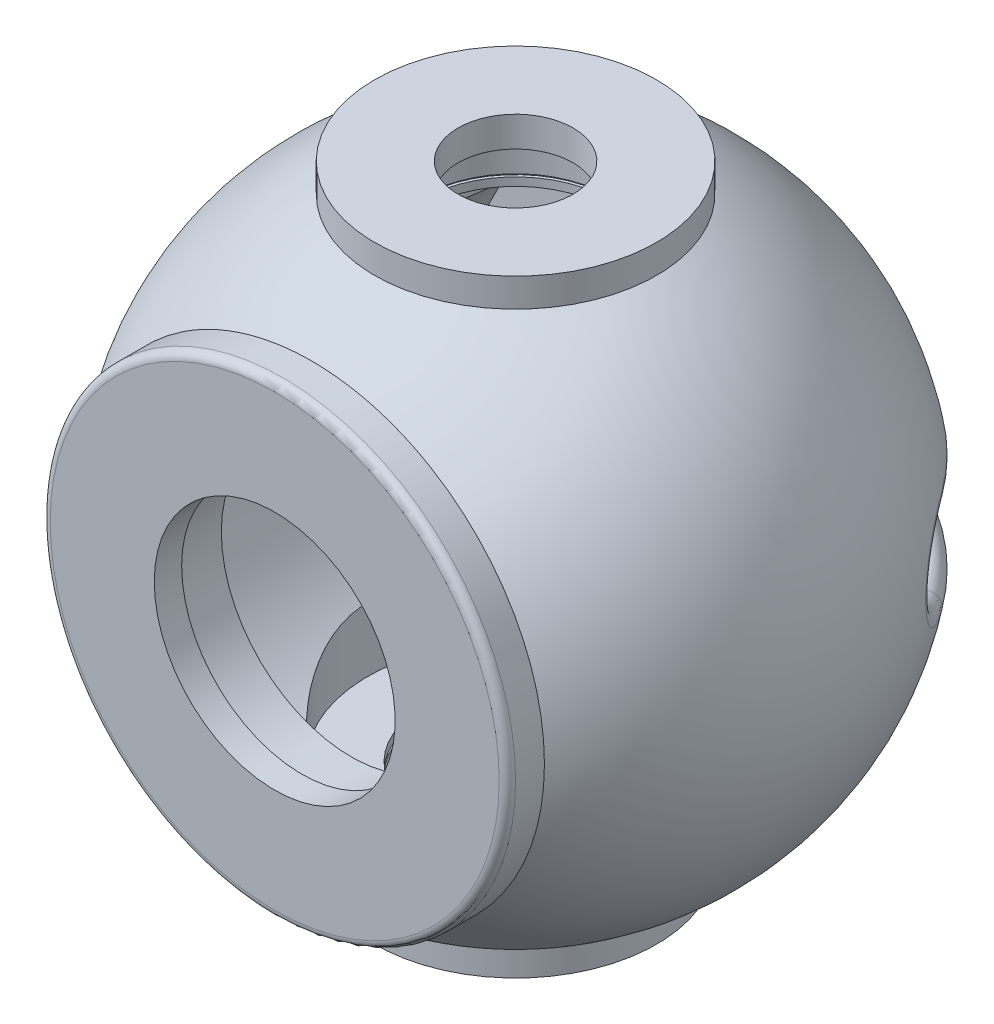
SolidWorks part; units mm, degrees
ref_plane "前视基准面" through (0, 0, 0) normal (0, 0, 1) x (1, 0, 0)
ref_plane "上视基准面" through (0, 0, 0) normal (0, 1, 0) x (1, 0, 0)
ref_plane "右视基准面" through (0, 0, 0) normal (1, 0, 0) x (0, 0, -1)
sketch "Sketch1" plane through (0, 0, 0) normal (0, 0, 1) x (1, 0, 0)
  line L0 (0, 113) -> (0, -113)
  arc A0 (0, -113) -> (0, 113) centre (0, 0) ccw
  dimension "D1" = 113
revolve "Revolve1" add sketch "Sketch1" angle 360 about L0
ref_plane "Plane1" through (0, 0, 120) normal (0, 0, 1) x (1, 0, 0)
sketch "Sketch5" plane through (0, 0, 0) normal (1, 0, 0) x (0, 0, -1)
  line L0 (0, 0) -> (0, 113) construction
  line L1 (31, 100) -> (21, 100)
  line L2 (31, 100) -> (31, 98)
  line L3 (31, 98) -> (34, 98)
  line L4 (34, 98) -> (34, 83)
  line L5 (34, 83) -> (35, 83)
  line L6 (35, 83) -> (35, 82)
  line L7 (35, 82) -> (34, 82)
  line L8 (34, 82) -> (34, 79)
  line L9 (21, 100) -> (21, 111.0315)
  line L10 (34, 79) -> (54, 79)
  line L11 (54, 79) -> (54, 0)
  line L12 (54, 0) -> (0, 0)
  line L13 (0, 0) -> (0, 113)
  line L14 (0, 0) -> (-48.9472, 0) construction
  circle A0 centre (0, 0) radius 113 construction
  arc A1 (21, 111.0315) -> (0, 113) centre (0, 0) ccw
  dimension "D1" = 15
  dimension "D2" = 68
  dimension "D3" = 62
  dimension "D4" = 2
  dimension "D5" = 1
  dimension "D6" = 1
  dimension "D7" = 42
  dimension "D8" = 3
  dimension "D9" = 20
  dimension "D10" = 158
revolve "Cut-Revolve1" cut sketch "Sketch5" angle 360 about L13
mirror "Mirror1" about plane through (0, 0, 0) normal (0, 1, 0) of "Cut-Revolve1"
ref_plane "Plane2" through (0, 0, 113) normal (0, 0, 1) x (1, 0, 0)
sketch "Sketch6" plane through (0, 0, 113) normal (0, 0, 1) x (1, 0, 0)
  circle A0 centre (0, 0) radius 85
  dimension "D1" = 170
extrude "Extrude2" add sketch "Sketch6" against normal up to next
sketch "Sketch9" plane through (0, 0, 0) normal (0, 1, 0) x (1, 0, 0)
  line L0 (0, -113) -> (0, -178.0384) construction
  line L1 (-122.1347, -113) -> (122.1347, -113) construction
  line L6 (44, -78) -> (47.5, -78)
  line L7 (47.5, -78) -> (47.5, -60)
  line L8 (47.5, -60) -> (77.5, -60)
  line L9 (77.5, -60) -> (77.5, 61.0929)
  line L10 (77.5, 61.0929) -> (0, 61.0929)
  line L11 (0, 61.0929) -> (0, -113)
  line L12 (43.9013, 115.9048) -> (121.2669, 38.5392) construction
  line L13 (0, 0) -> (79.9031, 79.9031) construction
  line L14 (0, 0) -> (104.9882, 0) construction
  line L16 (44, -78) -> (44, -88)
  line L19 (44, -88) -> (85, -88)
  line L20 (85, -113) -> (85, -74.458) construction
  line L21 (85, -88) -> (85, -113)
  line L22 (85, -113) -> (0, -113)
  dimension "D2" = 88
  dimension "D3" = 10
  dimension "D4" = 95
  dimension "D5" = 155
  dimension "D6" = 18
  dimension "D7" = 25
  dimension "D8" = 45
  dimension "D9" = 15
  dimension "D10" = 113
revolve "Cut-Revolve3" cut sketch "Sketch9" angle 360 about L0
ref_plane "Plane3" through (0, 111.0315, 0) normal (0, 1, 0) x (1, 0, 0)
sketch "Sketch11" plane through (0, 111.0315, 0) normal (0, 1, 0) x (1, 0, 0)
  circle A0 centre (0, 0) radius 51.5
  circle A1 centre (0, 0) radius 21 construction
  circle A2 centre (0, 0) radius 21
  dimension "D1" = 103
extrude "Extrude5" add sketch "Sketch11" against normal up to next
mirror "Mirror2" about plane through (0, 0, 0) normal (0, 1, 0) of "Extrude5"
sketch "Sketch12" plane through (0, 0, 0) normal (1, 0, 0) x (0, 0, -1)
  line L0 (63, 0) -> (113, 0) construction
  line L1 (63, 13) -> (113, 13)
  line L2 (63, -13) -> (113, -13)
  arc A0 (63, 13) -> (63, -13) centre (63, 0) ccw
  arc A1 (113, -13) -> (113, 13) centre (113, 0) ccw
  arc A2 (51.5, -100.5821) -> (51.5, 100.5821) centre (0, 0) ccw construction
  point P3 (88, 0)
  dimension "D1" = 13
  dimension "D2" = 63
extrude "Extrude6" cut sketch "Sketch12" against normal through all both and the other way through all
fillet "Fillet1" radius 5 4 edges at (-101.1328, -2.8956, -50.3266) (0, 13, -112.2497) (101.1328, 2.8956, -50.3266) (0, -13, -112.2497)
fillet "Fillet2" radius 3 1 edges at (-85, 0, 88)
sketch "Sketch14" plane through (0, 0, 0) normal (0, 1, 0) x (1, 0, 0)
  line L0 (0, 0) -> (-113, 0) construction
  line L1 (-112, 15) -> (-112, -15)
  line L2 (-112, 15) -> (-121.2168, 15)
  line L3 (-121.2168, 15) -> (-121.2168, -15)
  line L4 (-121.2168, -15) -> (-112, -15)
  arc A0 (-102.7237, 47.0833) -> (-85, -74.458) centre (0, 0) ccw construction
  dimension "D1" = 1
extrude "Extrude7" cut sketch "Sketch14" against normal through all both and the other way through all
